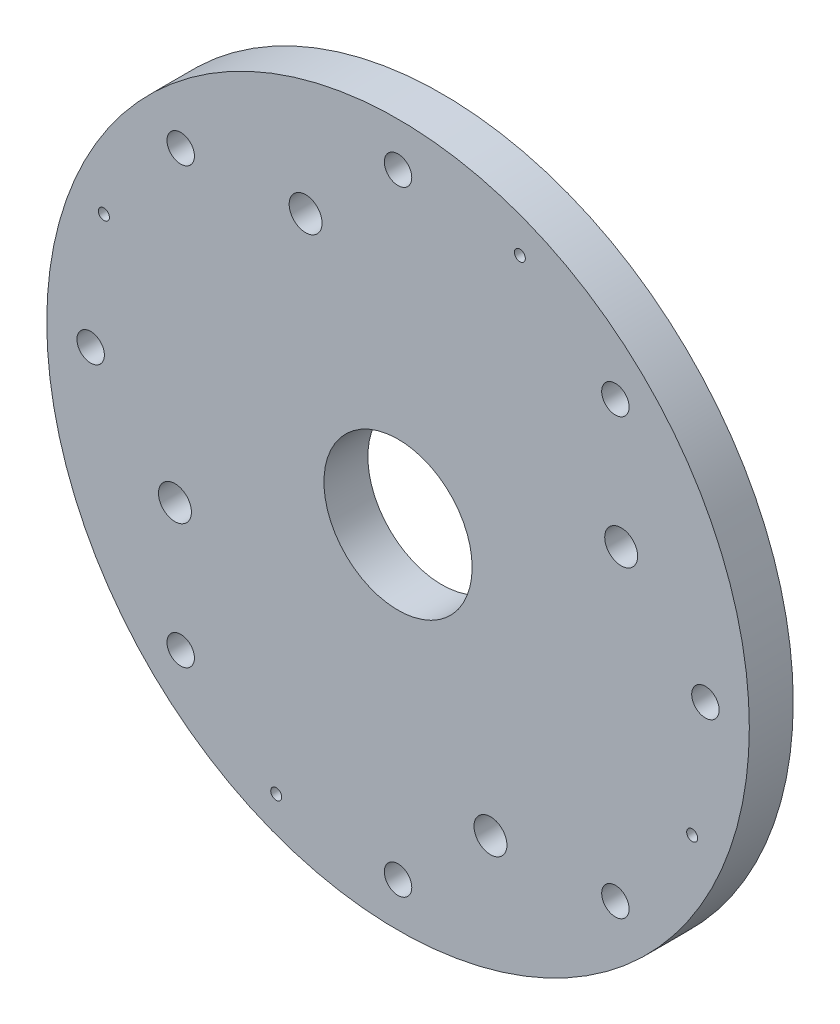
SolidWorks part; units mm, degrees
ref_plane "Alzado" through (0, 0, 0) normal (0, 0, 1) x (1, 0, 0)
ref_plane "Planta" through (0, 0, 0) normal (0, 1, 0) x (1, 0, 0)
ref_plane "Vista lateral" through (0, 0, 0) normal (1, 0, 0) x (0, 0, -1)
sketch "Croquis1" plane through (0, 0, 0) normal (0, 0, 1) x (1, 0, 0)
  circle A0 centre (0, 0) radius 32
  dimension "D1" = 64
extrude "Saliente-Extruir1" add sketch "Croquis1" along normal blind 4
sketch "Croquis2" plane through (0, 0, 4) normal (0, 0, 1) x (1, 0, 0)
  line L0 (0, 0) -> (0, 28) construction
  line L1 (0, 0) -> (19.799, 19.799) construction
  line L2 (0, 0) -> (28, 0) construction
  line L3 (0, 0) -> (19.799, -19.799) construction
  line L4 (0, 0) -> (0, -28) construction
  line L5 (0, 0) -> (-19.799, -19.799) construction
  line L6 (0, 0) -> (-28, 0) construction
  line L7 (0, 0) -> (-19.799, 19.799) construction
  circle A0 centre (0, 28) radius 1.25
  circle A1 centre (0, 0) radius 32 construction
  circle A2 centre (19.799, 19.799) radius 1.25
  circle A3 centre (28, 0) radius 1.25
  circle A4 centre (19.799, -19.799) radius 1.25
  circle A5 centre (0, -28) radius 1.25
  circle A6 centre (-19.799, -19.799) radius 1.25
  circle A7 centre (-28, 0) radius 1.25
  circle A8 centre (-19.799, 19.799) radius 1.25
  point P19 (0, 0)
  dimension "D1" = 2.5
  dimension "D2" = 28
  dimension "D3" = 8
extrude "Cortar-Extruir1" cut sketch "Croquis2" against normal through all
sketch "Croquis3" plane through (0, 0, 4) normal (0, 0, 1) x (1, 0, 0)
  circle A0 centre (0, 0) radius 6.75
  dimension "D1" = 13.5
extrude "Cortar-Extruir2" cut sketch "Croquis3" against normal blind 10
sketch "Croquis4" plane through (0, 0, 0) normal (0, 0, -1) x (-1, 0, 0)
  line L0 (-19.799, 19.799) -> (0, 28) construction
  line L1 (-9.8995, 23.8995) -> (-12.2459, 29.5641) construction
  line L2 (-12.2459, 29.5641) -> (-11.0978, 26.7925) construction
  circle A1 centre (0, 0) radius 32 construction
  circle A2 centre (-11.0978, 26.7925) radius 0.5
  circle A3 centre (0, 0) radius 32 construction
  circle A4 centre (26.7925, 11.0978) radius 0.5
  circle A5 centre (11.0978, -26.7925) radius 0.5
  circle A6 centre (-26.7925, -11.0978) radius 0.5
  point P9 (-9.8995, 23.8995)
  point P31 (0, 0)
  dimension "D1" = 1
  dimension "D2" = 3
  dimension "D3" = 4
extrude "Cortar-Extruir3" cut sketch "Croquis4" against normal blind 10
sketch "Croquis5" plane through (0, 0, 0) normal (0, 0, -1) x (-1, 0, 0)
  line L0 (0, 28) -> (19.799, 19.799) construction
  line L1 (9.8995, 23.8995) -> (12.2459, 29.5641) construction
  line L2 (12.2459, 29.5641) -> (8.419, 20.3253) construction
  circle A0 centre (0, 0) radius 32 construction
  circle A1 centre (8.419, 20.3253) radius 1.5
  circle A2 centre (20.3253, -8.419) radius 1.5
  circle A3 centre (-8.419, -20.3253) radius 1.5
  circle A4 centre (-20.3253, 8.419) radius 1.5
  point P10 (3.4309, -1.2167)
  point P19 (0, 0)
  dimension "D1" = 3
  dimension "D2" = 10
  dimension "D3" = 4
extrude "Cortar-Extruir4" cut sketch "Croquis5" against normal blind 10
sketch "Croquis6" plane through (0, 0, 0) normal (0, 0, 1) x (1, 0, 0)
  line L0 (-26.7925, 11.0978) -> (0, 0) construction
  line L1 (6.5713, 21.0907) -> (10.2668, 19.56)
  line L2 (-21.0907, 6.5713) -> (-17.3952, 5.0405)
  line L3 (-21.0907, 6.5713) -> (-19.56, 10.2668)
  line L4 (-19.56, 10.2668) -> (-15.8645, 8.7361)
  line L5 (-17.3952, 5.0405) -> (-15.8645, 8.7361)
  line L6 (-21.0907, 6.5713) -> (-15.8645, 8.7361) construction
  line L7 (-19.56, 10.2668) -> (-17.3952, 5.0405) construction
  line L8 (6.5713, 21.0907) -> (5.0405, 17.3952)
  line L9 (5.0405, 17.3952) -> (8.7361, 15.8645)
  line L10 (10.2668, 19.56) -> (8.7361, 15.8645)
  line L11 (21.0907, -6.5713) -> (19.56, -10.2668)
  line L12 (21.0907, -6.5713) -> (17.3952, -5.0405)
  line L13 (17.3952, -5.0405) -> (15.8645, -8.7361)
  line L14 (19.56, -10.2668) -> (15.8645, -8.7361)
  line L15 (-6.5713, -21.0907) -> (-10.2668, -19.56)
  line L16 (-6.5713, -21.0907) -> (-5.0405, -17.3952)
  line L17 (-5.0405, -17.3952) -> (-8.7361, -15.8645)
  line L18 (-10.2668, -19.56) -> (-8.7361, -15.8645)
  point P4 (-18.4776, 7.6537)
  point P9 (18.2927, -11.0133)
  point P10 (0, 0)
  point P24 (0, 0)
  dimension "D1" = 4
  dimension "D2" = 4
  dimension "D3" = 20
  dimension "D4" = 4
extrude "Saliente-Extruir3" add sketch "Croquis6" against normal blind 5
sketch "Croquis7" plane through (-8.419, -20.3253, 0) normal (-0.3827, -0.9239, 0) x (0.9239, -0.3827, 0)
  line L0 (0, 0) -> (0, -5) construction
  line L1 (-2, -5) -> (2, -5) construction
  circle A0 centre (0, -2.5) radius 0.75
  point P9 (0, -2.5)
  dimension "D1" = 1.5
extrude "Cortar-Extruir5" cut sketch "Croquis7" against normal through all
pattern_circular "MatrizC1" count 4 over 360 about axis through (0, 0, -6) along (0, 0, 1) of "Cortar-Extruir5"
